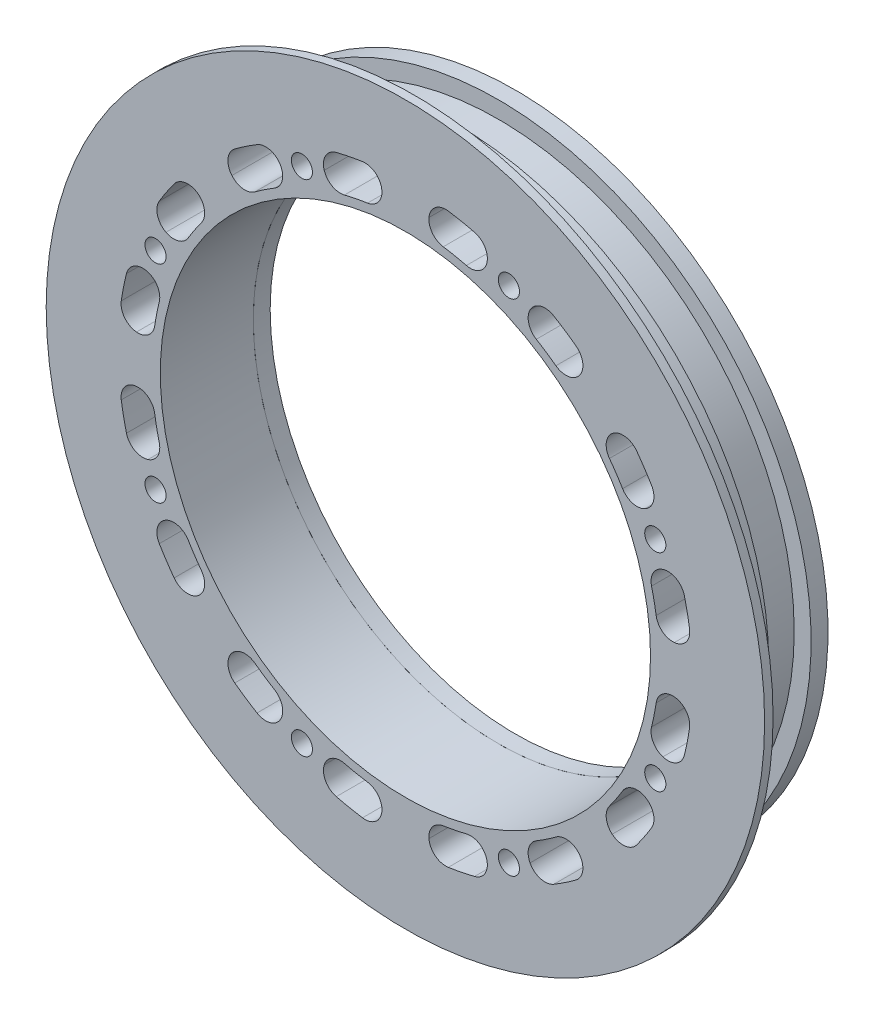
SolidWorks part; units mm, degrees
ref_plane "前视基准面" through (0, 0, 0) normal (0, 0, 1) x (1, 0, 0)
ref_plane "上视基准面" through (0, 0, 0) normal (0, 1, 0) x (1, 0, 0)
ref_plane "右视基准面" through (0, 0, 0) normal (1, 0, 0) x (0, 0, -1)
other "Configuration Table"
sketch "草图1" plane through (0, 0, 0) normal (0, 0, 1) x (1, 0, 0)
  circle A0 centre (0, 0) radius 35
  dimension "D1" = 70
extrude "凸台-拉伸1" add sketch "草图1" along normal blind 5
sketch "草图2" plane through (0, 0, 5) normal (0, 0, 1) x (1, 0, 0)
  circle A0 centre (0, 0) radius 37
  dimension "D1" = 74
extrude "凸台-拉伸2" add sketch "草图2" along normal blind 2
sketch "草图3" plane through (0, 0, 0) normal (0, 0, -1) x (-1, 0, 0)
  circle A0 centre (0, 0) radius 37
  circle A1 centre (0, 0) radius 37 construction
extrude "凸台-拉伸3" add sketch "草图3" along normal blind 2 separate body
sketch "草图4" plane through (0, 0, 7) normal (0, 0, 1) x (1, 0, 0)
  circle A0 centre (0, 0) radius 29
  dimension "D1" = 58
extrude "切除-拉伸1" cut sketch "草图4" against normal blind 20
sketch "草图5" plane through (0, 0, -2) normal (0, 0, -1) x (-1, 0, 0)
  circle A1 centre (0, 0) radius 32.5 construction
  circle A2 centre (0, 32.5) radius 2
  circle A3 centre (22.981, 22.981) radius 2
  circle A4 centre (32.5, 0) radius 2
  circle A5 centre (22.981, -22.981) radius 2
  circle A6 centre (0, -32.5) radius 2
  circle A7 centre (-22.981, -22.981) radius 2
  circle A8 centre (-32.5, 0) radius 2
  circle A9 centre (-22.981, 22.981) radius 2
  point P21 (0, 0)
  dimension "D1" = 65
  dimension "D2" = 4
  dimension "D3" = 8
extrude "切除-拉伸2" cut sketch "草图5" against normal blind 2
sketch "草图6" plane through (0, 0, 0) normal (0, 0, -1) x (-1, 0, 0)
  circle A0 centre (0, 32.5) radius 1.65
  circle A1 centre (22.981, 22.981) radius 1.65
  circle A2 centre (32.5, 0) radius 1.65
  circle A3 centre (22.981, -22.981) radius 1.65
  circle A4 centre (0, -32.5) radius 1.65
  circle A5 centre (-22.981, -22.981) radius 1.65
  circle A6 centre (-32.5, 0) radius 1.65
  circle A7 centre (-22.981, 22.981) radius 1.65
  point P20 (0, 0)
  dimension "D1" = 3.3
  dimension "D2" = 8
extrude "切除-拉伸3" cut sketch "草图6" against normal blind 8
sketch "草图7" plane through (0, 0, 7) normal (0, 0, 1) x (1, 0, 0)
  circle A0 centre (0, 0) radius 37
  circle A1 centre (0, 0) radius 29
  circle A2 centre (0, 0) radius 29 construction
  circle A3 centre (0, 0) radius 37 construction
extrude "凸台-拉伸4" add sketch "草图7" along normal blind 4
sketch "草图8" plane through (0, 0, 11) normal (0, 0, 1) x (1, 0, 0)
  line L0 (0, 32) -> (0, 0) construction
  line L1 (0, 0) -> (12.2459, 29.5641) construction
  circle A0 centre (0, 0) radius 32 construction
  circle A1 centre (12.2459, 29.5641) radius 1.25
  circle A3 centre (29.5641, 12.2459) radius 1.25
  circle A4 centre (29.5641, -12.2459) radius 1.25
  circle A5 centre (12.2459, -29.5641) radius 1.25
  circle A6 centre (-12.2459, -29.5641) radius 1.25
  circle A7 centre (-29.5641, -12.2459) radius 1.25
  circle A8 centre (-29.5641, 12.2459) radius 1.25
  circle A9 centre (-12.2459, 29.5641) radius 1.25
  point P23 (0, 0)
  dimension "D1" = 2.5
  dimension "D2" = 64
  dimension "D4" = 22.5
  dimension "D3" = 8
extrude "切除-拉伸4" cut sketch "草图8" against normal blind 20
sketch "草图9" plane through (0, 0, -2) normal (0, 0, -1) x (-1, 0, 0)
  line L0 (0, 32.5) -> (0, 0) construction
  line L1 (0, 0) -> (22.981, 22.981) construction
  line L2 (4.5032, 34.2048) -> (0, 0)
  line L3 (0, 0) -> (21.0023, 27.3707)
  circle A0 centre (0, 0) radius 31.5
  circle A1 centre (0, 0) radius 34.5
  circle A2 centre (0, 0) radius 37 construction
  dimension "D1" = 2.5
  dimension "D2" = 3
  dimension "D3" = 7.5
  dimension "D4" = 7.5
extrude "切除-拉伸5" cut sketch "草图9" against normal up to surface (2 mm away) contours L3 A1 L2 A0 region at (-12.4934, 30.1617, -2) up to face at (-2, 32.5, 0)
pattern_circular "阵列(圆周)1" count 8 every 45 about axis through (0, 0, -2) along (0, 0, -1) of "切除-拉伸5"
fillet "圆角1" radius 1.5 32 edges at (-4.1116, 31.2305, -1) (-4.5032, 34.2048, -1) (-21.0023, 27.3707, -1) (-19.176, 24.9906, -1) (-24.9906, 19.176, -1) (-27.3707, 21.0023, -1) (-34.2048, 4.5032, -1) (-31.2305, 4.1116, -1) (-31.2305, -4.1116, -1) (-34.2048, -4.5032, -1) (-27.3707, -21.0023, -1) (-24.9906, -19.176, -1) (-19.176, -24.9906, -1) (-21.0023, -27.3707, -1) (-4.5032, -34.2048, -1) (-4.1116, -31.2305, -1) (4.1116, -31.2305, -1) (4.5032, -34.2048, -1) (21.0023, -27.3707, -1) (19.176, -24.9906, -1) (24.9906, -19.176, -1) (27.3707, -21.0023, -1) (34.2048, -4.5032, -1) (31.2305, -4.1116, -1) (31.2305, 4.1116, -1) (34.2048, 4.5032, -1) (27.3707, 21.0023, -1) (24.9906, 19.176, -1) (21.0023, 27.3707, -1) (4.5032, 34.2048, -1) (4.1116, 31.2305, -1) (19.176, 24.9906, -1)
sketch "草图10" plane through (0, 0, 0) normal (0, 0, -1) x (-1, 0, 0)
  line L0 (0, 32.5) -> (0, 0) construction
  line L1 (0, 0) -> (12.2459, 29.5641) construction
  line L2 (2.9633, 33.8706) -> (0, 0)
  line L3 (0, 0) -> (10.224, 32.4264)
  circle A0 centre (0, 0) radius 30
  circle A1 centre (0, 0) radius 34
  circle A2 centre (0, 0) radius 29 construction
  circle A3 centre (0, 0) radius 35 construction
  dimension "D3" = 1
  dimension "D4" = 1
  dimension "D1" = 5
  dimension "D2" = 5
extrude "切除-拉伸6" cut sketch "草图10" against normal up to surface (11 mm away) contours L3 A1 L2 A0 region at (-6.2386, 31.3637, 0) up to face at (30.8141, 12.2459, 11)
pattern_circular "阵列(圆周)2" count 16 every 22.5 about axis through (0, 0, 20.2499) along (0, 0, -1) of "切除-拉伸6"
fillet "圆角2" radius 2 64 edges at (-10.224, 32.4264, 5.5) (-9.0212, 28.6115, 5.5) (-2.9633, 33.8706, 5.5) (-2.6147, 29.8858, 5.5) (-21.8548, 26.0455, 5.5) (-19.2836, 22.9813, 5.5) (-15.6995, 30.1584, 5.5) (2.9633, 33.8706, 5.5) (2.6147, 29.8858, 5.5) (9.0212, 28.6115, 5.5) (10.224, 32.4264, 5.5) (15.6995, 30.1584, 5.5) (13.8525, 26.6103, 5.5) (19.2836, 22.9813, 5.5) (21.8548, 26.0455, 5.5) (26.0455, 21.8548, 5.5) (22.9813, 19.2836, 5.5) (26.6103, 13.8525, 5.5) (30.1584, 15.6995, 5.5) (32.4264, 10.224, 5.5) (28.6115, 9.0212, 5.5) (29.8858, 2.6147, 5.5) (33.8706, 2.9633, 5.5) (33.8706, -2.9633, 5.5) (29.8858, -2.6147, 5.5) (28.6115, -9.0212, 5.5) (32.4264, -10.224, 5.5) (30.1584, -15.6995, 5.5) (26.6103, -13.8525, 5.5) (22.9813, -19.2836, 5.5) (26.0455, -21.8548, 5.5) (21.8548, -26.0455, 5.5) (19.2836, -22.9813, 5.5) (13.8525, -26.6103, 5.5) (15.6995, -30.1584, 5.5) (10.224, -32.4264, 5.5) (9.0212, -28.6115, 5.5) (2.6147, -29.8858, 5.5) (2.9633, -33.8706, 5.5) (-2.9633, -33.8706, 5.5) (-2.6147, -29.8858, 5.5) (-9.0212, -28.6115, 5.5) (-10.224, -32.4264, 5.5) (-15.6995, -30.1584, 5.5) (-13.8525, -26.6103, 5.5) (-19.2836, -22.9813, 5.5) (-21.8548, -26.0455, 5.5) (-26.0455, -21.8548, 5.5) (-22.9813, -19.2836, 5.5) (-26.6103, -13.8525, 5.5) (-30.1584, -15.6995, 5.5) (-32.4264, -10.224, 5.5) (-28.6115, -9.0212, 5.5) (-29.8858, -2.6147, 5.5) (-33.8706, -2.9633, 5.5) (-33.8706, 2.9633, 5.5) (-29.8858, 2.6147, 5.5) (-28.6115, 9.0212, 5.5) (-32.4264, 10.224, 5.5) (-30.1584, 15.6995, 5.5) (-26.6103, 13.8525, 5.5) (-22.9813, 19.2836, 5.5) (-26.0455, 21.8548, 5.5) (-13.8525, 26.6103, 5.5)
sketch "草图11" plane through (0, 0, 11) normal (0, 0, 1) x (1, 0, 0)
  circle A0 centre (0, 0) radius 42.5
  circle A1 centre (0, 0) radius 37 construction
  circle A2 centre (0, 0) radius 37
  dimension "D1" = 85
extrude "凸台-拉伸5" add sketch "草图11" against normal blind 1
sketch "草图12" plane through (0, 0, 11) normal (0, 0, 1) x (1, 0, 0)
  circle A1 centre (0, 0) radius 42.5
  circle A4 centre (0, 0) radius 42.5
  dimension "D1" = 0
extrude "切除-拉伸7" [suppressed] cut sketch "草图12" against normal up to surface (1 mm away)
